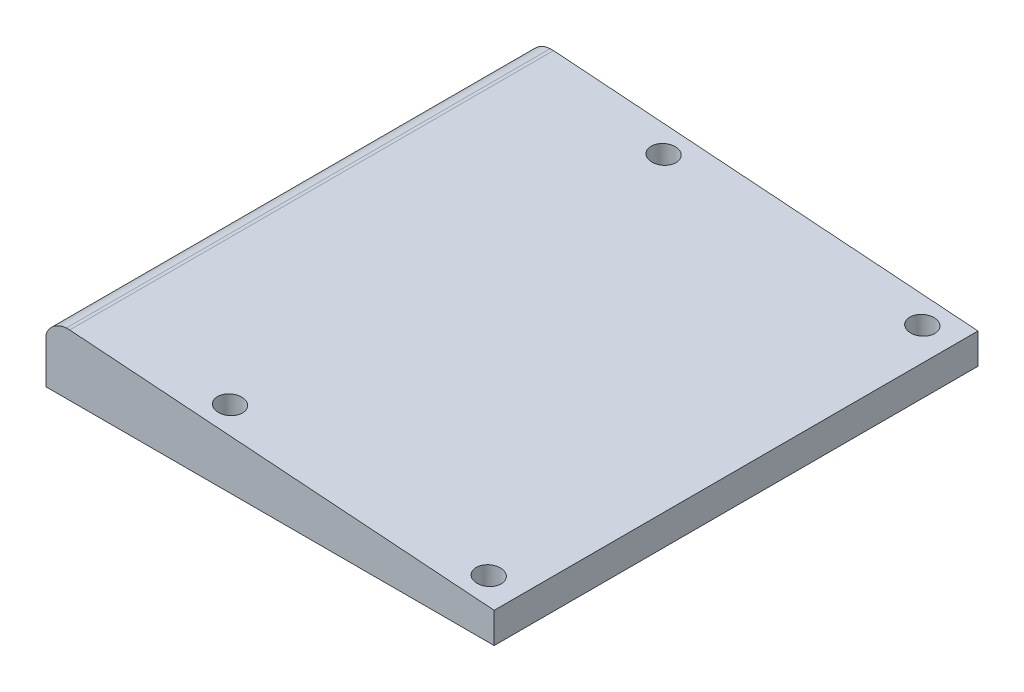
SolidWorks part; units mm, degrees
ref_plane "Front Plane" through (0, 0, 0) normal (0, 0, 1) x (1, 0, 0)
ref_plane "Top Plane" through (0, 0, 0) normal (0, 1, 0) x (1, 0, 0)
ref_plane "Right Plane" through (0, 0, 0) normal (1, 0, 0) x (0, 0, -1)
sketch "Sketch1" plane through (0, 0, 0) normal (0, 1, 0) x (1, 0, 0)
  line L0 (-121, 0) -> (121, 0) construction
  line L1 (-110, -118.75) -> (110, -118.75)
  line L2 (-110, -118.75) -> (-110, 118.75)
  line L3 (-110, 118.75) -> (110, 118.75)
  line L4 (110, -118.75) -> (110, 118.75)
  line L5 (-110, -118.75) -> (110, 118.75) construction
  line L6 (-110, 118.75) -> (110, -118.75) construction
  point P0 (0, 0)
  point P6 (95, 106.42)
  point P7 (-32, 106.42)
  point P8 (0, 0)
  point P13 (95, -106.42)
  point P14 (-32, -106.42)
  point P15 (0, 0)
  dimension "D1" = 220
  dimension "D2" = 237.5
  dimension "D3" = 12.33
  dimension "D4" = 15
  dimension "D5" = 127
extrude "Boss-Extrude1" add sketch "Sketch1" along normal blind 30
sketch "Sketch2" plane through (0, 0, 0) normal (0, 0, 1) x (1, 0, 0)
  line L0 (110, 15) -> (-98.3922, 30)
  line L1 (110, 30) -> (110, 0) construction
  line L2 (-110, 30) -> (110, 30) construction
  line L3 (-110, 30) -> (-110, 0) construction
  line L4 (-110, 30) -> (110, 30)
  line L5 (110, 30) -> (110, 15)
  arc A0 (-98.3922, 30) -> (-110, 15) centre (-99.2098, 18.6413) ccw
  arc A1 (-110, 15) -> (-110, 30) centre (-87.7754, 22.5) cw
extrude "Cut-Extrude1" cut sketch "Sketch2" against normal through all both and the other way through all contours L5 L4 L0 | A1 A0 L4 | A0 A1 L4 L5 L0 region at (-108.455, 26.6598, 0) region at (40.5359, 25, 0)
ref_plane "Plane1" through (0, 30.0294, 0) normal (0, 1, 0) x (1, 0, 0)
hole_wizard "CBORE for M5 Hex Head Bolt1" positions "Sketch8" profile "Sketch6" counterbore size "M5" standard "ANSI Metric" end condition through all
sketch "Sketch8" plane through (0, 30.0294, 0) normal (0, 1, 0) x (1, 0, 0)
  point P0 (-32, 106.42)
  point P3 (95, 106.42)
  point P6 (95, -106.42)
  point P9 (-32, -106.42)
sketch "Sketch6" plane through (-32, 30.0294, -106.42) normal (1, 0, 0) x (0, 0, 1)
  line L0 (0, 0) -> (0, 30.0294)
  line L1 (0, 30.0294) -> (2.75, 30.0294)
  line L3 (2.75, 30.0294) -> (2.75, 23.58)
  line L4 (2.75, 23.58) -> (6.12, 23.58)
  line L5 (6.12, 23.58) -> (6.12, 0)
  line L7 (6.12, 0) -> (0, 0)
  line L11 (0, -6.35) -> (0, 107.95) construction
  dimension "Thru Hole Dia." = 5.5
  dimension "Thru Hole Depth" = 30.0294
  dimension "C'Bore Dia." = 12.24
  dimension "C'Bore Depth" = 23.58
